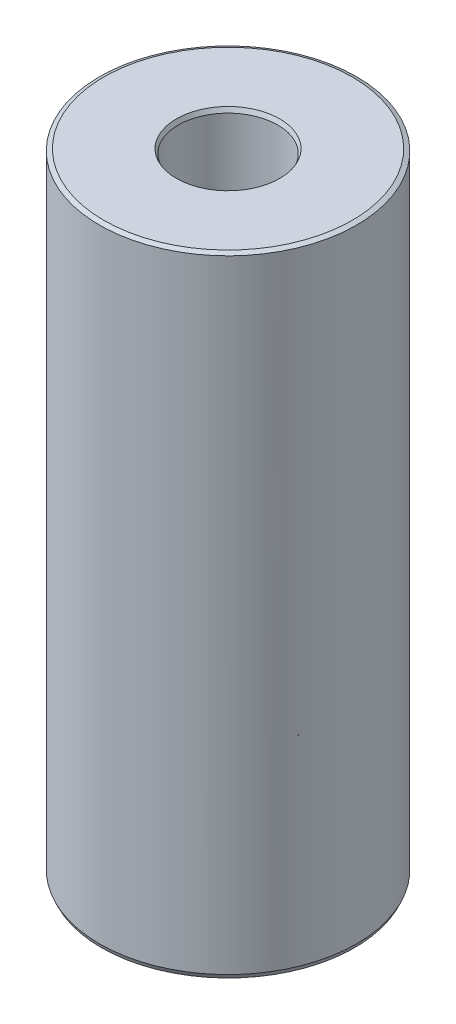
SolidWorks part; units mm, degrees
ref_plane "Front Plane" through (0, 0, 0) normal (0, 0, 1) x (1, 0, 0)
ref_plane "Top Plane" through (0, 0, 0) normal (0, 1, 0) x (1, 0, 0)
ref_plane "Right Plane" through (0, 0, 0) normal (1, 0, 0) x (0, 0, -1)
sketch "Sketch1" plane through (0, 0, 0) normal (0, 1, 0) x (1, 0, 0)
  circle A0 centre (0, 0) radius 57.5
  dimension "SLEEVE_OD" = 115
extrude "Boss-Extrude1" add sketch "Sketch1" along normal blind 281.2272
sketch "Sketch2" plane through (0, 0, 0) normal (0, 1, 0) x (1, 0, 0)
  circle A0 centre (0, 0) radius 22.2293
  dimension "BORE_D" = 44.4586
extrude "Cut-Extrude1" cut sketch "Sketch2" along normal through all
chamfer "Chamfer1" distance 0.8751 angle 65.778 4 edges at (0, 281.2272, 22.2293) (0, 0, 22.2293) (0, 0, 57.5) (0, 281.2272, 57.5) first distance on face at (0, 281.2272, 22.2293) first distance on face at (0, 0, 22.2293) first distance on face at (0, 281.2272, 57.5)
